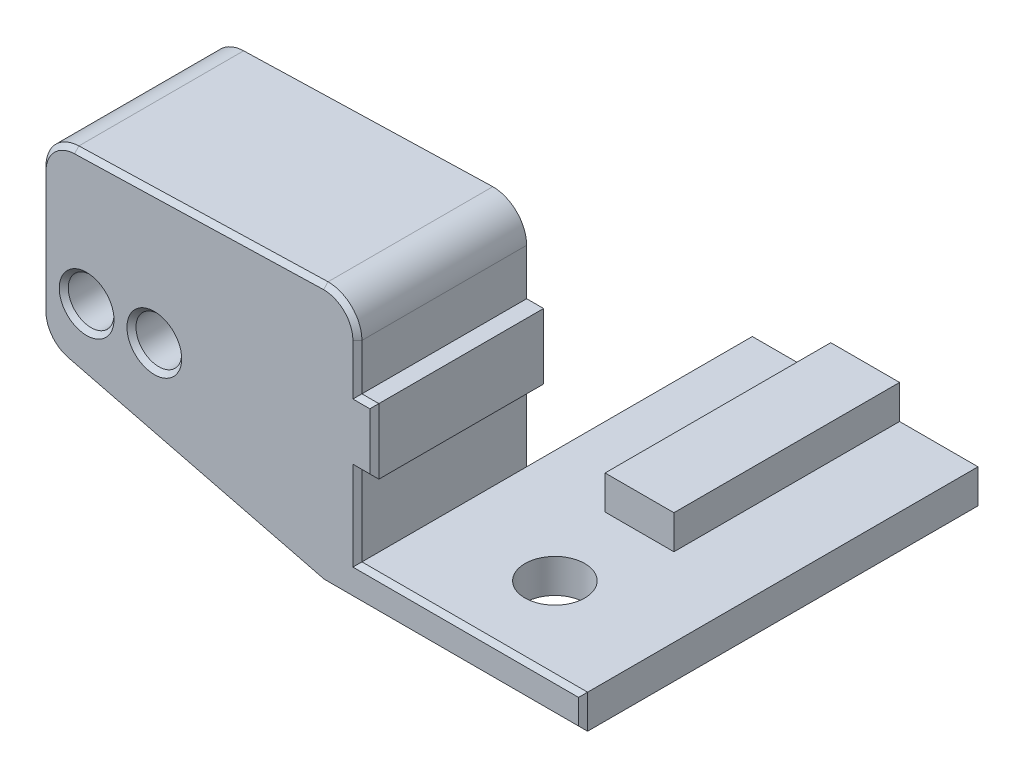
SolidWorks part; units mm, degrees
ref_plane "Front Plane" through (0, 0, 0) normal (0, 0, 1) x (1, 0, 0)
ref_plane "Top Plane" through (0, 0, 0) normal (0, 1, 0) x (1, 0, 0)
ref_plane "Right Plane" through (0, 0, 0) normal (1, 0, 0) x (0, 0, -1)
sketch "Sketch1" plane through (0, 0, 0) normal (0, 0, 1) x (1, 0, 0)
  line L0 (45.4899, -84.3159) -> (51.4899, -84.3159) construction
  line L1 (48.4899, -84.3159) -> (66.4899, -84.3159) construction
  line L2 (66.4899, -72.3159) -> (69.4899, -72.3159)
  line L3 (48.4899, -77.3159) -> (48.4899, -84.3159) construction
  line L4 (41.4899, -73.0103) -> (41.4899, -89.0659)
  line L7 (66.4899, -95.3159) -> (89.4899, -95.3159)
  line L9 (69.4899, -72.3159) -> (69.4899, -79.4159)
  line L10 (69.4899, -92.3159) -> (76.5899, -92.3159)
  line L11 (89.4899, -92.3159) -> (89.4899, -95.3159)
  line L12 (76.5899, -92.3159) -> (82.3899, -92.3159)
  line L14 (41.4899, -89.0659) -> (66.4899, -95.3159)
  line L17 (48.4899, -77.3159) -> (66.4899, -77.3159) construction
  line L18 (66.4899, -72.3159) -> (41.4899, -73.0103)
  line L19 (48.4899, -84.3159) -> (48.4899, -90.8159) construction
  line L20 (48.4899, -84.3159) -> (41.4899, -84.3159) construction
  line L21 (48.4899, -84.3159) -> (48.4899, -72.8159) construction
  line L22 (66.4899, -77.3159) -> (66.4899, -95.3159) construction
  line L23 (89.4899, 311.6195) -> (89.4899, -188.3805) construction
  line L29 (69.4899, -85.2159) -> (70.9899, -85.2159)
  line L31 (69.4899, -79.4159) -> (70.9899, -79.4159)
  line L32 (70.9899, -85.2159) -> (70.9899, -79.4159)
  line L33 (69.4899, -82.3159) -> (70.9899, -82.3159) construction
  line L34 (82.3899, -92.3159) -> (89.4899, -92.3159)
  line L35 (69.4899, -85.2159) -> (69.4899, -92.3159)
  circle A0 centre (48.4899, -77.3159) radius 3.025
  circle A1 centre (45.4899, -84.3159) radius 2.025
  circle A2 centre (51.4899, -84.3159) radius 2.025
  dimension "D3" = 4.05
  dimension "D4" = 6.05
  dimension "D1" = 3
  dimension "D2" = 6
  dimension "D5" = 6.5
  dimension "D6" = 7
  dimension "D7" = 11.5
  dimension "D8" = 23
  dimension "D9" = 25
  dimension "D10" = 20
  dimension "D11" = 20
  dimension "D12" = 8
  dimension "D13" = 5.8
extrude "Boss-Extrude1" add sketch "Sketch1" along normal blind 15
extrude "Boss-Extrude2" add sketch "Sketch1<2>" along normal up to surface (15 mm away) from offset 5.6 contours A0 region at (48.4899, -77.3159, 0) up to face at (47.5149, -84.3159, 15)
sketch "Sketch1<2>" plane through (0, 0, 0) normal (0, 0, 1) x (1, 0, 0) same geometry as "Sketch1"
sketch "Sketch3" plane through (0, 0, 0) normal (0, 0, -1) x (-1, 0, 0)
  line L0 (-76.4399, -92.3159) -> (-69.4899, -92.3159)
  line L1 (-89.4899, -95.3159) -> (-69.4899, -95.3159)
  line L2 (-89.4899, -95.3159) -> (-89.4899, -92.3159)
  line L3 (-89.4899, -92.3159) -> (-82.5399, -92.3159)
  line L4 (-69.4899, -95.3159) -> (-69.4899, -92.3159)
  line L6 (-82.5399, -92.3159) -> (-82.5399, -89.3159)
  line L7 (-82.5399, -89.3159) -> (-76.4399, -89.3159)
  line L8 (-76.4399, -92.3159) -> (-76.4399, -89.3159)
  dimension "D1" = 6.1
  dimension "D2" = 3
extrude "Boss-Extrude3" add sketch "Sketch3" along normal blind 20
sketch "Sketch2" plane through (0, -95.3159, 0) normal (0, -1, 0) x (1, 0, 0)
  line L0 (89.4899, 0) -> (69.4899, 15) construction
  line L1 (66.4899, 15) -> (89.4899, 15) construction
  line L2 (69.4899, 15) -> (89.4899, 15) construction
  line L3 (69.4899, 0) -> (89.4899, 0) construction
  line L4 (89.4899, 15) -> (89.4899, -20) construction
  circle A0 centre (79.4899, 7.5) radius 2.65
  point P10 (89.4899, 0)
  dimension "D2" = 5.3
  dimension "D1" = 20
extrude "Cut-Extrude1" cut sketch "Sketch2" against normal blind 70
ref_plane "Plane1" through (0, 0, 25) normal (0, 0, 1) x (1, 0, 0)
fillet "Fillet1" radius 3 3 edges at (69.4899, -72.3159, 7.5) (41.4899, -73.0103, 7.5) (41.4899, -89.0659, 7.5)
chamfer "Chamfer1" distance 0.4 angle 45 16 edges at (53.5149, -84.3159, 15) (70.2399, -79.4159, 15) (70.9899, -82.3159, 15) (70.2399, -85.2159, 15) (69.4899, -88.7659, 15) (79.4899, -92.3159, 15) (89.4899, -93.8159, 15) (77.9899, -95.3159, 15) (55.1261, -92.4749, 15) (42.1253, -88.5698, 15) (41.4899, -81.3258, 15) (42.3394, -73.8365, 15) (55.4483, -72.6226, 15) (68.6112, -73.1945, 15) (69.4899, -77.3659, 15) (47.5149, -84.3159, 15)
